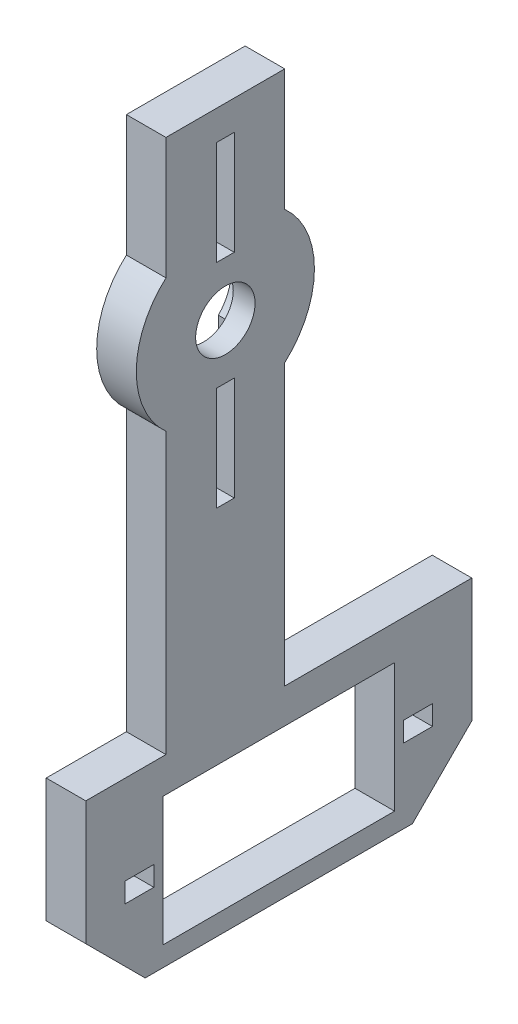
SolidWorks part; units mm, degrees
ref_plane "Front Plane" through (0, 0, 0) normal (0, 0, 1) x (1, 0, 0)
ref_plane "Top Plane" through (0, 0, 0) normal (0, 1, 0) x (1, 0, 0)
ref_plane "Right Plane" through (0, 0, 0) normal (1, 0, 0) x (0, 0, -1)
sketch "Sketch1" plane through (0, 0, 0) normal (1, 0, 0) x (0, 0, -1)
  circle A0 centre (52, -20) radius 9
extrude "Boss-Extrude1" add sketch "Sketch1" along normal blind 4 from offset 66.4
sketch "Sketch2" plane through (0, 0, 0) normal (0, 0, 1) x (1, 0, 0)
  line L1 (66.4, -56) -> (70.4, -56)
  line L2 (66.4, -56) -> (66.4, -1)
  line L3 (66.4, -1) -> (70.4, -1)
  line L4 (70.4, -56) -> (70.4, -1)
extrude "Boss-Extrude2" add sketch "Sketch2" along normal blind 12 from offset 58 offset against normal yes
sketch "Sketch3" plane through (0, 0, 0) normal (0, 0, 1) x (1, 0, 0)
  line L1 (66.4, -73.5) -> (70.4, -73.5)
  line L2 (66.4, -73.5) -> (66.4, -55)
  line L3 (66.4, -55) -> (70.4, -55)
  line L4 (70.4, -73.5) -> (70.4, -55)
extrude "Boss-Extrude3" add sketch "Sketch3" along normal blind 39 from offset 76.9 offset against normal yes
sketch "Sketch4" plane through (0, 0, 0) normal (1, 0, 0) x (0, 0, -1)
  line L0 (36.9, -74.5) -> (44.9, -74.5)
  line L1 (44.9, -74.5) -> (36.9, -66.5)
  line L2 (36.9, -66.5) -> (36.9, -74.5)
extrude "Boss-Extrude4" add sketch "Sketch4" along normal blind 6 from offset 65.4 separate body
combine bodies "Combine1" operation type subtract main body 103 bodies to subtract 104
sketch "Sketch5" plane through (0, 0, 0) normal (1, 0, 0) x (0, 0, -1)
  line L0 (77.9, -74.5) -> (69.9, -74.5)
  line L1 (69.9, -74.5) -> (77.9, -66.5)
  line L2 (77.9, -66.5) -> (77.9, -74.5)
extrude "Boss-Extrude5" add sketch "Sketch5" along normal blind 6 from offset 65.4 separate body
combine bodies "Combine2" operation type subtract main body 105 bodies to subtract 106
sketch "Sketch6" plane through (0, 0, 0) normal (1, 0, 0) x (0, 0, -1)
  circle A0 centre (52, -20) radius 4.6
extrude "Boss-Extrude6" add sketch "Sketch6" along normal blind 2.3 from offset 65.9 separate body
combine bodies "Combine3" operation type subtract main body 107 bodies to subtract 108
sketch "Sketch7" plane through (0, 0, 0) normal (0, 0, 1) x (1, 0, 0)
  line L1 (65.9, -20) -> (68.2, -20)
  line L2 (65.9, -20) -> (65.9, -2.5)
  line L3 (65.9, -2.5) -> (68.2, -2.5)
  line L4 (68.2, -20) -> (68.2, -2.5)
extrude "Boss-Extrude7" add sketch "Sketch7" along normal blind 6.6 from offset 55.3 separate body offset against normal yes
combine bodies "Combine4" operation type subtract main body 109 bodies to subtract 110
sketch "Sketch8" plane through (0, 0, 0) normal (0, 0, 1) x (1, 0, 0)
  line L1 (65.4, -14.5) -> (71.4, -14.5)
  line L2 (65.4, -14.5) -> (65.4, -4)
  line L3 (65.4, -4) -> (71.4, -4)
  line L4 (71.4, -14.5) -> (71.4, -4)
extrude "Boss-Extrude8" add sketch "Sketch8" along normal blind 1.8 from offset 52.9 separate body offset against normal yes
combine bodies "Combine5" operation type subtract main body 111 bodies to subtract 112
sketch "Sketch9" plane through (0, 0, 0) normal (0, 0, 1) x (1, 0, 0)
  line L1 (65.9, -37.5) -> (68.2, -37.5)
  line L2 (65.9, -37.5) -> (65.9, -20)
  line L3 (65.9, -20) -> (68.2, -20)
  line L4 (68.2, -37.5) -> (68.2, -20)
extrude "Boss-Extrude9" add sketch "Sketch9" along normal blind 6.6 from offset 55.3 separate body offset against normal yes
combine bodies "Combine6" operation type subtract main body 113 bodies to subtract 114
sketch "Sketch10" plane through (0, 0, 0) normal (0, 0, 1) x (1, 0, 0)
  line L1 (65.4, -36) -> (71.4, -36)
  line L2 (65.4, -36) -> (65.4, -25.5)
  line L3 (65.4, -25.5) -> (71.4, -25.5)
  line L4 (71.4, -36) -> (71.4, -25.5)
extrude "Boss-Extrude10" add sketch "Sketch10" along normal blind 1.8 from offset 52.9 separate body offset against normal yes
combine bodies "Combine7" operation type subtract main body 115 bodies to subtract 116
sketch "Sketch11" plane through (0, 0, 0) normal (1, 0, 0) x (0, 0, -1)
  circle A0 centre (52, -20) radius 3
extrude "Boss-Extrude11" add sketch "Sketch11" along normal blind 6 from offset 65.4 separate body
combine bodies "Combine8" operation type subtract main body 117 bodies to subtract 118
sketch "Sketch12" plane through (0, 0, 0) normal (0, 0, 1) x (1, 0, 0)
  line L1 (65.4, -71.5) -> (71.4, -71.5)
  line L2 (65.4, -71.5) -> (65.4, -58.5)
  line L3 (65.4, -58.5) -> (71.4, -58.5)
  line L4 (71.4, -71.5) -> (71.4, -58.5)
extrude "Boss-Extrude12" add sketch "Sketch12" along normal blind 23.4 from offset 69.1 separate body offset against normal yes
combine bodies "Combine9" operation type subtract main body 119 bodies to subtract 120
sketch "Sketch13" plane through (0, 0, 0) normal (0, 0, 1) x (1, 0, 0)
  line L1 (65.4, -66) -> (71.4, -66)
  line L2 (65.4, -66) -> (65.4, -64)
  line L3 (65.4, -64) -> (71.4, -64)
  line L4 (71.4, -66) -> (71.4, -64)
extrude "Boss-Extrude13" add sketch "Sketch13" along normal blind 2.9 from offset 72.925 separate body offset against normal yes
combine bodies "Combine10" operation type subtract main body 121 bodies to subtract 122
sketch "Sketch14" plane through (0, 0, 0) normal (0, 0, 1) x (1, 0, 0)
  line L1 (65.4, -66) -> (71.4, -66)
  line L2 (65.4, -66) -> (65.4, -64)
  line L3 (65.4, -64) -> (71.4, -64)
  line L4 (71.4, -66) -> (71.4, -64)
extrude "Boss-Extrude14" add sketch "Sketch14" along normal blind 2.9 from offset 44.775 separate body offset against normal yes
combine bodies "Combine11" operation type subtract main body 123 bodies to subtract 124
